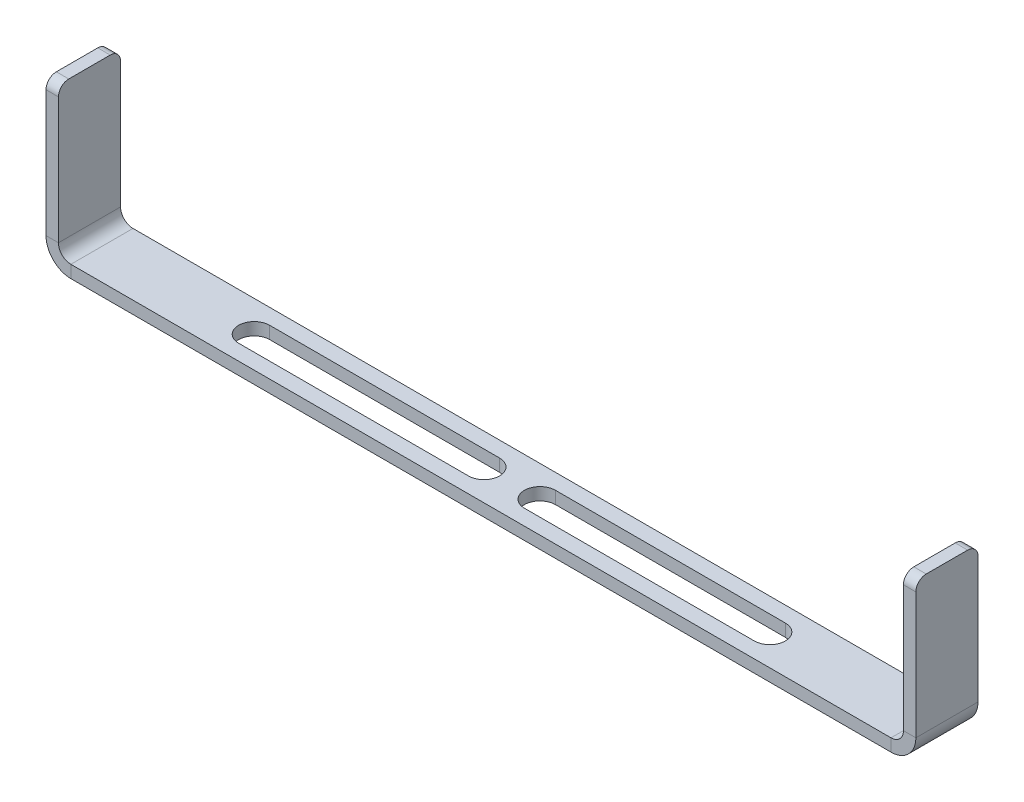
SolidWorks part; units mm, degrees
note: The reader was unsure of these and kept them because the rebuilt part matched: thickness of "基体-法兰1", "钣金6", "钣金7"; bend radius of "基体折弯1", "基体折弯2".
material "Q355"
ref_plane "前视基准面" through (0, 0, 0) normal (0, 0, 1) x (1, 0, 0)
ref_plane "上视基准面" through (0, 0, 0) normal (0, 1, 0) x (1, 0, 0)
ref_plane "右视基准面" through (0, 0, 0) normal (1, 0, 0) x (0, 0, -1)
sketch "草图1" plane through (0, 0, 0) normal (0, 0, 1) x (1, 0, 0)
  line L0 (0, 0) -> (0, 127.1968) construction
  line L1 (204, 0) -> (-204, 0)
  line L2 (-204, 0) -> (-204, 72)
  line L3 (204, 0) -> (204, 72)
  dimension "D1" = 72
  dimension "D2" = 408
base flange "基体-法兰1" sketch "草图1" end condition mid plane depth 30 reverse direction no thickness 6 reverse thickness direction no bend radius 6
bend "基体折弯1" bend radius 6 bend angle 90 parameters "D5"=1
bend "基体折弯2" bend radius 6 bend angle 90 parameters "D5"=2
sketch "草图6" plane through (0, -6, 0) normal (0, -1, 0) x (1, 0, 0)
  line L0 (0, 0) -> (234.6502, 0) construction
  line L1 (0, 0) -> (0, 41.7611) construction
  line L2 (13.5, 0) -> (124.5, 0) construction
  line L3 (13.5, 7.5) -> (124.5, 7.5)
  line L4 (13.5, -7.5) -> (124.5, -7.5)
  line L5 (-13.5, 0) -> (-124.5, 0) construction
  line L6 (-13.5, 7.5) -> (-124.5, 7.5)
  line L7 (-13.5, -7.5) -> (-124.5, -7.5)
  arc A0 (13.5, 7.5) -> (13.5, -7.5) centre (13.5, 0) ccw
  arc A1 (124.5, -7.5) -> (124.5, 7.5) centre (124.5, 0) ccw
  arc A2 (-13.5, 7.5) -> (-13.5, -7.5) centre (-13.5, 0) cw
  arc A3 (-124.5, -7.5) -> (-124.5, 7.5) centre (-124.5, 0) cw
  point P6 (69, 0)
  point P13 (-69, 0)
  dimension "D2" = 7.5
  dimension "D1" = 111
  dimension "D3" = 27
extrude "切除-拉伸1" cut sketch "草图6" against normal blind 10 normal cut yes
fillet "圆角1" radius 5 4 edges at (207, 72, -15) (207, 72, 15) (-207, 72, -15) (-207, 72, 15)
sketch "折弯-线1" [suppressed] plane through (0, 0, 0) normal (0, 1, 0) x (1, 0, 0)
sketch "边界框1" [suppressed] plane through (0, 0, 0) normal (0, 1, 0) x (1, 0, 0)
sheet metal parameters "钣金6" thickness 6 parameters "D1"=4, "D7"=8
flat pattern "平板型式6" [suppressed]
sketch "折弯-线2" plane through (0, 0, 0) normal (0, 1, 0) x (1, 0, 0)
sketch "边界框2" [suppressed] plane through (0, 0, 0) normal (0, 1, 0) x (1, 0, 0)
bend of the flat pattern "展开-<基体折弯1>1"
bend of the flat pattern "展开-<基体折弯2>1"
sheet metal parameters "钣金7" thickness 6 parameters "D1"=4, "D7"=8
flat pattern "平板型式6"
sketch "折弯-线2" plane through (0, 0, 0) normal (0, 1, 0) x (1, 0, 0)
  line L0 (-205.0686, -15) -> (-205.0686, 15) construction
  line L1 (205.0686, 15) -> (205.0686, -15) construction
  line L2 (-205.0686, -15) -> (-205.0686, 15) construction
  line L3 (205.0686, 15) -> (205.0686, -15) construction
sketch3d "边界框2" [suppressed]
  line L0 (74.1372, 0, 0) -> (-482.1372, 0, 0) construction
  line L1 (74.1372, 30, 0) -> (-482.1372, 30, 0) construction
  line L2 (74.1372, 0, 0) -> (74.1372, 30, 0) construction
  line L3 (-482.1372, 0, 0) -> (-482.1372, 30, 0) construction
bend of the flat pattern "展开-<基体折弯1>1"
bend of the flat pattern "展开-<基体折弯2>1"
